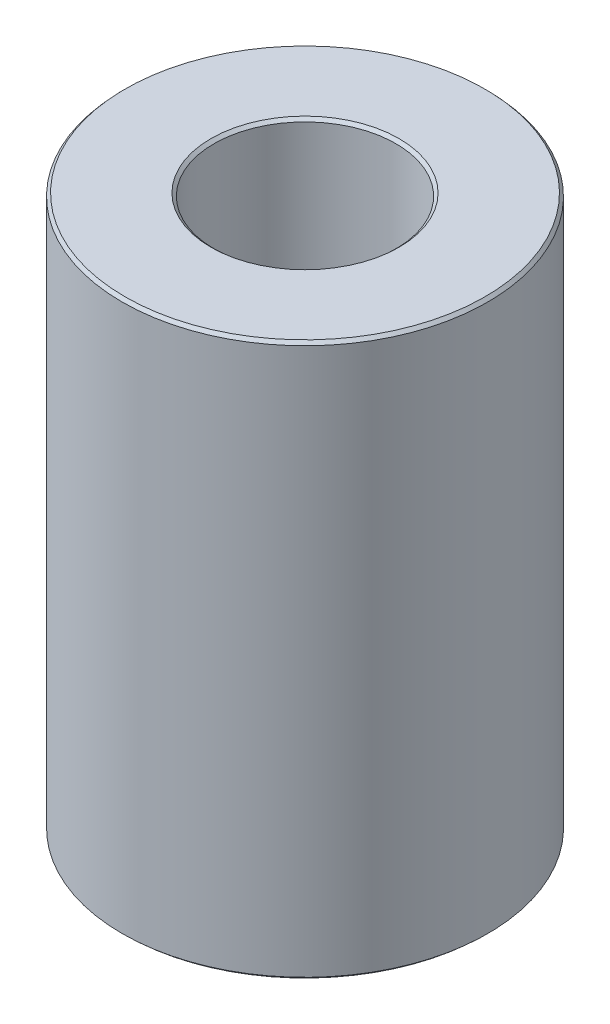
SolidWorks part; units mm, degrees
ref_plane "Front Plane" through (0, 0, 0) normal (0, 0, 1) x (1, 0, 0)
ref_plane "Top Plane" through (0, 0, 0) normal (0, 1, 0) x (1, 0, 0)
ref_plane "Right Plane" through (0, 0, 0) normal (1, 0, 0) x (0, 0, -1)
sketch "Sketch1" plane through (0, 0, 0) normal (0, 1, 0) x (1, 0, 0)
  circle A0 centre (0, 0) radius 50
  dimension "SLEEVE_OD" = 100
extrude "Boss-Extrude1" add sketch "Sketch1" along normal blind 151.2458
sketch "Sketch2" plane through (0, 0, 0) normal (0, 1, 0) x (1, 0, 0)
  circle A0 centre (0, 0) radius 24.8915
  dimension "BORE_D" = 49.783
extrude "Cut-Extrude1" cut sketch "Sketch2" along normal through all
chamfer "Chamfer1" distance 0.8541 angle 42.254 4 edges at (0, 151.2458, 24.8915) (0, 0, 24.8915) (0, 0, 50) (0, 151.2458, 50) first distance on face at (0, 151.2458, 24.8915) first distance on face at (0, 0, 24.8915) first distance on face at (0, 151.2458, 50)
